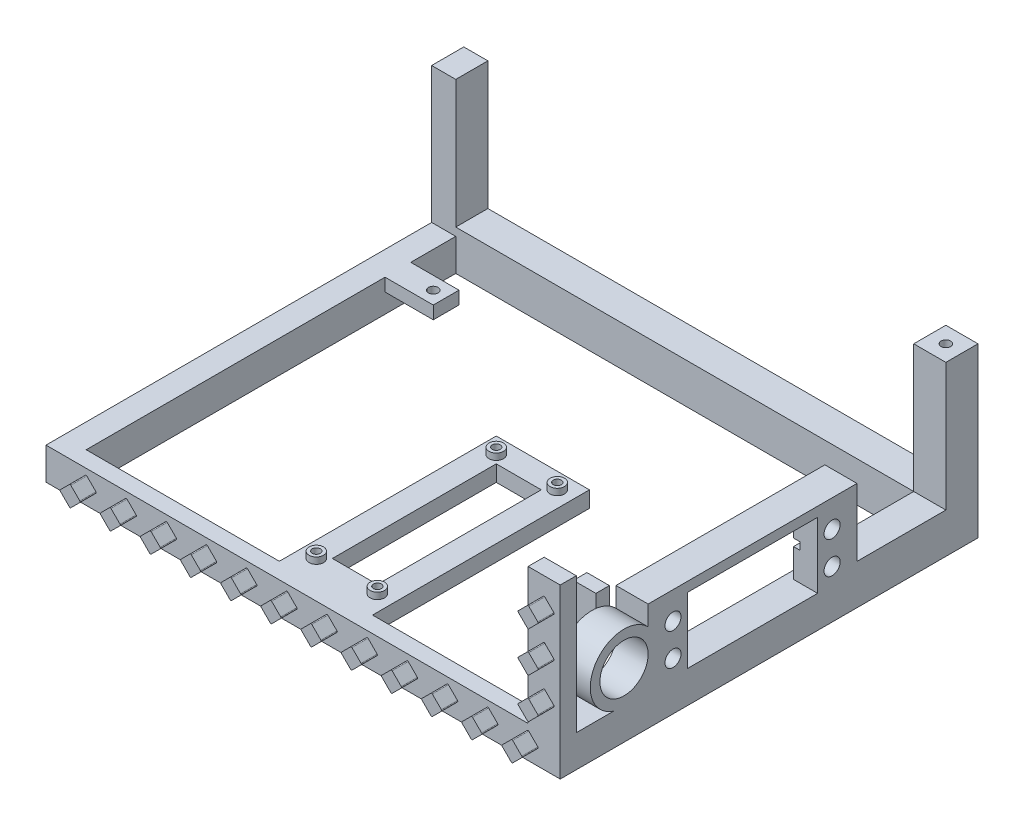
SolidWorks part; units mm, degrees
other "Markup1"
sketch "Sketch27" plane through (-85, 52.3, 65) normal (-0.8972, 0.4289, 0.105) x (0.3802, 0.6295, 0.6776)
ref_plane "Front Plane" through (0, 0, 0) normal (0, 0, 1) x (1, 0, 0)
ref_plane "Top Plane" through (0, 0, 0) normal (0, 1, 0) x (1, 0, 0)
ref_plane "Right Plane" through (0, 0, 0) normal (1, 0, 0) x (0, 0, -1)
sketch "Sketch1" plane through (0, 0, 0) normal (0, 1, 0) x (1, 0, 0)
  line L0 (0, 0) -> (0, 70) construction
  line L1 (-85, -60) -> (75, -60)
  line L2 (-85, -60) -> (-85, 70)
  line L3 (-85, 70) -> (75, 70)
  line L4 (75, -60) -> (75, 70)
  line L5 (0, 0) -> (0, -60) construction
  point P0 (0, 0)
  dimension "D1" = 160
  dimension "D2" = 70
  dimension "D3" = 60
extrude "Boss-Extrude1" add sketch "Sketch1" along normal blind 10
sketch "Sketch2" plane through (0, 10, 0) normal (0, 1, 0) x (1, 0, 0)
  line L0 (-85, 70) -> (75, 70)
  line L4 (-85, 70) -> (-85, 60)
  line L5 (-85, 70) -> (-85, -60) construction
  line L6 (-85, 60) -> (65, 60)
  line L13 (75, 70) -> (75, -60)
  line L14 (75, -60) -> (65, -60)
  line L15 (-85, -60) -> (75, -60) construction
  line L16 (65, -60) -> (65, 60)
extrude "Boss-Extrude2" add sketch "Sketch2" along normal blind 42.3
sketch "Sketch6" plane through (0, 0, 60) normal (0, 0, 1) x (1, 0, 0)
  line L0 (65, 10) -> (75, 10) construction
  line L1 (75, 52.3) -> (75, 0) construction
  line L2 (69.7879, 40.6121) -> (66.9621, 43.4379)
  line L79 (65, 10) -> (65, 0) construction
  line L156 (-85, 0) -> (75, 0) construction
  line L157 (66.9621, 43.8621) -> (69.7879, 46.6879)
  line L158 (70.2121, 46.6879) -> (73.0379, 43.8621)
  line L159 (70, 10) -> (70, 52.3) construction
  line L160 (65, 52.3) -> (75, 52.3) construction
  line L185 (65, 5) -> (-85, 5) construction
  line L186 (-85, 10) -> (-85, 0) construction
  line L187 (-10, 8.25) -> (-10, 1.75) construction
  line L188 (-10.2121, 8.0379) -> (-13.0379, 5.2121)
  line L189 (-13.0379, 4.7879) -> (-10.2121, 1.9621)
  line L190 (-9.7879, 1.9621) -> (-6.9621, 4.7879)
  line L191 (-6.9621, 5.2121) -> (-9.7879, 8.0379)
  line L192 (73.25, 31.15) -> (66.75, 31.15) construction
  line L193 (66.9621, 31.3621) -> (69.7879, 34.1879)
  line L194 (70.2121, 34.1879) -> (73.0379, 31.3621)
  line L195 (73.0379, 30.9379) -> (70.2121, 28.1121)
  line L196 (69.7879, 28.1121) -> (66.9621, 30.9379)
  line L197 (5.5379, 5.2121) -> (2.7121, 8.0379)
  line L198 (2.2879, 8.0379) -> (-0.5379, 5.2121)
  line L199 (-0.5379, 4.7879) -> (2.2879, 1.9621)
  line L200 (2.7121, 1.9621) -> (5.5379, 4.7879)
  line L201 (18.0379, 5.2121) -> (15.2121, 8.0379)
  line L202 (14.7879, 8.0379) -> (11.9621, 5.2121)
  line L203 (11.9621, 4.7879) -> (14.7879, 1.9621)
  line L204 (15.2121, 1.9621) -> (18.0379, 4.7879)
  line L205 (30.5379, 5.2121) -> (27.7121, 8.0379)
  line L206 (27.2879, 8.0379) -> (24.4621, 5.2121)
  line L207 (24.4621, 4.7879) -> (27.2879, 1.9621)
  line L208 (27.7121, 1.9621) -> (30.5379, 4.7879)
  line L209 (43.0379, 5.2121) -> (40.2121, 8.0379)
  line L210 (39.7879, 8.0379) -> (36.9621, 5.2121)
  line L211 (36.9621, 4.7879) -> (39.7879, 1.9621)
  line L212 (40.2121, 1.9621) -> (43.0379, 4.7879)
  line L213 (55.5379, 5.2121) -> (52.7121, 8.0379)
  line L214 (52.2879, 8.0379) -> (49.4621, 5.2121)
  line L215 (49.4621, 4.7879) -> (52.2879, 1.9621)
  line L216 (52.7121, 1.9621) -> (55.5379, 4.7879)
  line L217 (68.0379, 5.2121) -> (65.2121, 8.0379)
  line L218 (64.7879, 8.0379) -> (61.9621, 5.2121)
  line L219 (61.9621, 4.7879) -> (64.7879, 1.9621)
  line L220 (65.2121, 1.9621) -> (68.0379, 4.7879)
  line L221 (-19.4621, 5.2121) -> (-22.2879, 8.0379)
  line L222 (-22.7121, 8.0379) -> (-25.5379, 5.2121)
  line L223 (-25.5379, 4.7879) -> (-22.7121, 1.9621)
  line L224 (-22.2879, 1.9621) -> (-19.4621, 4.7879)
  line L225 (-31.9621, 5.2121) -> (-34.7879, 8.0379)
  line L226 (-35.2121, 8.0379) -> (-38.0379, 5.2121)
  line L227 (-38.0379, 4.7879) -> (-35.2121, 1.9621)
  line L228 (-34.7879, 1.9621) -> (-31.9621, 4.7879)
  line L229 (-44.4621, 5.2121) -> (-47.2879, 8.0379)
  line L230 (-47.7121, 8.0379) -> (-50.5379, 5.2121)
  line L231 (-50.5379, 4.7879) -> (-47.7121, 1.9621)
  line L232 (-47.2879, 1.9621) -> (-44.4621, 4.7879)
  line L233 (-56.9621, 5.2121) -> (-59.7879, 8.0379)
  line L234 (-60.2121, 8.0379) -> (-63.0379, 5.2121)
  line L235 (-63.0379, 4.7879) -> (-60.2121, 1.9621)
  line L236 (-59.7879, 1.9621) -> (-56.9621, 4.7879)
  line L237 (-69.4621, 5.2121) -> (-72.2879, 8.0379)
  line L238 (-72.7121, 8.0379) -> (-75.5379, 5.2121)
  line L239 (-75.5379, 4.7879) -> (-72.7121, 1.9621)
  line L240 (-72.2879, 1.9621) -> (-69.4621, 4.7879)
  line L241 (73.0379, 43.4379) -> (70.2121, 40.6121)
  line L242 (69.7879, 15.6121) -> (66.9621, 18.4379)
  line L243 (66.9621, 18.8621) -> (69.7879, 21.6879)
  line L244 (70.2121, 21.6879) -> (73.0379, 18.8621)
  line L245 (73.0379, 18.4379) -> (70.2121, 15.6121)
  arc A128 (-13.0379, 5.2121) -> (-13.0379, 4.7879) centre (-12.8257, 5) ccw
  arc A129 (-9.7879, 1.9621) -> (-10.2121, 1.9621) centre (-10, 2.1743) cw
  arc A130 (-6.9621, 4.7879) -> (-6.9621, 5.2121) centre (-7.1743, 5) ccw
  arc A131 (-9.7879, 8.0379) -> (-10.2121, 8.0379) centre (-10, 7.8257) ccw
  arc A132 (66.9621, 30.9379) -> (66.9621, 31.3621) centre (67.1743, 31.15) cw
  arc A133 (70.2121, 28.1121) -> (69.7879, 28.1121) centre (70, 28.3243) cw
  arc A134 (73.0379, 30.9379) -> (73.0379, 31.3621) centre (72.8257, 31.15) ccw
  arc A135 (69.7879, 34.1879) -> (70.2121, 34.1879) centre (70, 33.9757) cw
  arc A136 (2.7121, 8.0379) -> (2.2879, 8.0379) centre (2.5, 7.8257) ccw
  arc A137 (5.5379, 4.7879) -> (5.5379, 5.2121) centre (5.3257, 5) ccw
  arc A138 (-0.5379, 5.2121) -> (-0.5379, 4.7879) centre (-0.3257, 5) ccw
  arc A139 (2.7121, 1.9621) -> (2.2879, 1.9621) centre (2.5, 2.1743) cw
  arc A140 (15.2121, 8.0379) -> (14.7879, 8.0379) centre (15, 7.8257) ccw
  arc A141 (18.0379, 4.7879) -> (18.0379, 5.2121) centre (17.8257, 5) ccw
  arc A142 (11.9621, 5.2121) -> (11.9621, 4.7879) centre (12.1743, 5) ccw
  arc A143 (15.2121, 1.9621) -> (14.7879, 1.9621) centre (15, 2.1743) cw
  arc A144 (27.7121, 8.0379) -> (27.2879, 8.0379) centre (27.5, 7.8257) ccw
  arc A145 (30.5379, 4.7879) -> (30.5379, 5.2121) centre (30.3257, 5) ccw
  arc A146 (24.4621, 5.2121) -> (24.4621, 4.7879) centre (24.6743, 5) ccw
  arc A147 (27.7121, 1.9621) -> (27.2879, 1.9621) centre (27.5, 2.1743) cw
  arc A148 (40.2121, 8.0379) -> (39.7879, 8.0379) centre (40, 7.8257) ccw
  arc A149 (43.0379, 4.7879) -> (43.0379, 5.2121) centre (42.8257, 5) ccw
  arc A150 (36.9621, 5.2121) -> (36.9621, 4.7879) centre (37.1743, 5) ccw
  arc A151 (40.2121, 1.9621) -> (39.7879, 1.9621) centre (40, 2.1743) cw
  arc A152 (52.7121, 8.0379) -> (52.2879, 8.0379) centre (52.5, 7.8257) ccw
  arc A153 (55.5379, 4.7879) -> (55.5379, 5.2121) centre (55.3257, 5) ccw
  arc A154 (49.4621, 5.2121) -> (49.4621, 4.7879) centre (49.6743, 5) ccw
  arc A155 (52.7121, 1.9621) -> (52.2879, 1.9621) centre (52.5, 2.1743) cw
  arc A156 (65.2121, 8.0379) -> (64.7879, 8.0379) centre (65, 7.8257) ccw
  arc A157 (68.0379, 4.7879) -> (68.0379, 5.2121) centre (67.8257, 5) ccw
  arc A158 (61.9621, 5.2121) -> (61.9621, 4.7879) centre (62.1743, 5) ccw
  arc A159 (65.2121, 1.9621) -> (64.7879, 1.9621) centre (65, 2.1743) cw
  arc A160 (-22.2879, 8.0379) -> (-22.7121, 8.0379) centre (-22.5, 7.8257) ccw
  arc A161 (-19.4621, 4.7879) -> (-19.4621, 5.2121) centre (-19.6743, 5) ccw
  arc A162 (-25.5379, 5.2121) -> (-25.5379, 4.7879) centre (-25.3257, 5) ccw
  arc A163 (-22.2879, 1.9621) -> (-22.7121, 1.9621) centre (-22.5, 2.1743) cw
  arc A164 (-34.7879, 8.0379) -> (-35.2121, 8.0379) centre (-35, 7.8257) ccw
  arc A165 (-31.9621, 4.7879) -> (-31.9621, 5.2121) centre (-32.1743, 5) ccw
  arc A166 (-38.0379, 5.2121) -> (-38.0379, 4.7879) centre (-37.8257, 5) ccw
  arc A167 (-34.7879, 1.9621) -> (-35.2121, 1.9621) centre (-35, 2.1743) cw
  arc A168 (-47.2879, 8.0379) -> (-47.7121, 8.0379) centre (-47.5, 7.8257) ccw
  arc A169 (-44.4621, 4.7879) -> (-44.4621, 5.2121) centre (-44.6743, 5) ccw
  arc A170 (-50.5379, 5.2121) -> (-50.5379, 4.7879) centre (-50.3257, 5) ccw
  arc A171 (-47.2879, 1.9621) -> (-47.7121, 1.9621) centre (-47.5, 2.1743) cw
  arc A172 (-59.7879, 8.0379) -> (-60.2121, 8.0379) centre (-60, 7.8257) ccw
  arc A173 (-56.9621, 4.7879) -> (-56.9621, 5.2121) centre (-57.1743, 5) ccw
  arc A174 (-63.0379, 5.2121) -> (-63.0379, 4.7879) centre (-62.8257, 5) ccw
  arc A175 (-59.7879, 1.9621) -> (-60.2121, 1.9621) centre (-60, 2.1743) cw
  arc A176 (-72.2879, 8.0379) -> (-72.7121, 8.0379) centre (-72.5, 7.8257) ccw
  arc A177 (-69.4621, 4.7879) -> (-69.4621, 5.2121) centre (-69.6743, 5) ccw
  arc A178 (-75.5379, 5.2121) -> (-75.5379, 4.7879) centre (-75.3257, 5) ccw
  arc A179 (-72.2879, 1.9621) -> (-72.7121, 1.9621) centre (-72.5, 2.1743) cw
  arc A180 (70.2121, 40.6121) -> (69.7879, 40.6121) centre (70, 40.8243) cw
  arc A181 (66.9621, 43.4379) -> (66.9621, 43.8621) centre (67.1743, 43.65) cw
  arc A182 (69.7879, 46.6879) -> (70.2121, 46.6879) centre (70, 46.4757) cw
  arc A183 (73.0379, 43.4379) -> (73.0379, 43.8621) centre (72.8257, 43.65) ccw
  arc A184 (70.2121, 15.6121) -> (69.7879, 15.6121) centre (70, 15.8243) cw
  arc A185 (66.9621, 18.4379) -> (66.9621, 18.8621) centre (67.1743, 18.65) cw
  arc A186 (69.7879, 21.6879) -> (70.2121, 21.6879) centre (70, 21.4757) cw
  arc A187 (73.0379, 18.4379) -> (73.0379, 18.8621) centre (72.8257, 18.65) ccw
  point P19 (-10, 5)
  point P22 (-13.25, 5)
  point P28 (-6.75, 5)
  point P35 (70, 31.15)
  point P42 (70, 27.9)
  point P48 (70, 34.4)
  dimension "D2" = 0.3
  dimension "D1" = 0.3
  dimension "D3" = 2
  dimension "D4" = 2
extrude "Boss-Extrude3" add sketch "Sketch6" along normal blind 5
sketch "Sketch7" plane through (0, 10, 0) normal (0, 1, 0) x (1, 0, 0)
  line L0 (-66.5, 42) -> (-66.5, 60) construction
  line L1 (-85, 60) -> (65, 60) construction
  line L2 (-85, 60) -> (-85, -60) construction
  line L4 (-66.5, 42) -> (-85, 42) construction
  circle A0 centre (-66.5, 42) radius 1.5
  dimension "D1" = 18
  dimension "D2" = 18.5
extrude "Cut-Extrude2" cut sketch "Sketch7" against normal through all
sketch "Sketch8" plane through (0, 10, 0) normal (0, 1, 0) x (1, 0, 0)
  line L5 (-77.5, 60) -> (65, 60)
  line L6 (-66.5, 42) -> (-75, 42) construction
  line L7 (-77.5, 46) -> (-62.5, 46)
  line L8 (-62.5, 46) -> (-62.5, 38)
  line L9 (-62.5, 38) -> (-77.5, 38)
  line L11 (-77.5, 60) -> (-77.5, 46)
  line L12 (-85, 60) -> (-85, -60) construction
  line L13 (-77.5, 38) -> (-77.5, -55)
  line L14 (65, 60) -> (65, -55)
  line L15 (65, 60) -> (65, -60) construction
  line L16 (65, -55) -> (-77.5, -55)
  circle A0 centre (-66.5, 42) radius 1.5 construction
  dimension "D3" = 4
  dimension "D2" = 7.5
  dimension "D4" = 4
  dimension "D5" = 4
extrude "Cut-Extrude3" cut sketch "Sketch8" against normal through all contours L13 L16 L14 L5 L11 L7 L8 L9
sketch "Sketch11" plane through (0, 52.3, 0) normal (0, 1, 0) x (1, 0, 0)
  line L0 (75, 70) -> (65, 60) construction
  circle A3 centre (70, 65) radius 1.5
extrude "Cut-Extrude6" cut sketch "Sketch11" against normal blind 4
sketch "Sketch12" plane through (0, 0, -60) normal (0, 0, 1) x (1, 0, 0)
  line L1 (-77.5, 52.3) -> (-77.5, 12.5)
  line L7 (-77.5, 52.3) -> (65, 52.3)
  line L10 (-85, 52.3) -> (65, 52.3) construction
  line L12 (65, 52.3) -> (65, 12.5)
  line L13 (65, 52.3) -> (65, 0) construction
  line L14 (65, 12.5) -> (-77.5, 12.5)
extrude "Cut-Extrude7" cut sketch "Sketch12" against normal through all
sketch "Sketch15" plane through (0, 10, 0) normal (0, 1, 0) x (1, 0, 0)
  line L0 (6.6, 7.5) -> (6.6, -48.5) construction
  line L1 (6.6, 7.5) -> (-12.4, 7.5) construction
  line L2 (6.6, -48.5) -> (-12.4, -48.5) construction
  line L3 (-17.4, 12.5) -> (11.6, 12.5)
  line L4 (11.6, 12.5) -> (11.6, -53.5)
  line L6 (-12.4, -48.5) -> (-12.4, 7.5) construction
  line L9 (11.6, -53.5) -> (-17.4, -53.5)
  line L10 (-17.4, -53.5) -> (-17.4, 12.5)
  line L11 (-12.4, 7.5) -> (6.6, 7.5) construction
  line L23 (-77.5, 38) -> (-77.5, -55) construction
  line L24 (4.1, 5) -> (-9.9, 5)
  line L25 (4.1, 5) -> (4.1, -46)
  line L26 (4.1, -46) -> (-9.9, -46)
  line L27 (-9.9, 5) -> (-9.9, -46)
  line L33 (6.6, -48.5) -> (-12.4, -48.5) construction
  line L35 (6.6, -18.8362) -> (11.6, -18.8362) construction
  line L36 (-12.4, -20.5) -> (-17.4, -20.5) construction
  line L37 (-2.9, -48.5) -> (-2.9, -53.5) construction
  line L42 (-17.4, -53.5) -> (-17.4, -55)
  line L44 (-17.4, -55) -> (11.6, -55)
  line L45 (11.6, -55) -> (11.6, -53.5)
  circle A0 centre (-12.4, 7.5) radius 1.25
  circle A1 centre (6.6, 7.5) radius 1.25
  circle A2 centre (-12.4, -48.5) radius 1.25
  circle A3 centre (6.6, -48.5) radius 1.25
  circle A4 centre (-12.4, 7.5) radius 2.25
  circle A5 centre (6.6, 7.5) radius 2.25
  circle A6 centre (-12.4, -48.5) radius 2.25
  circle A7 centre (6.6, -48.5) radius 2.25
  point P32 (-2.9, -18.8362)
  dimension "D1" = 60.1
  dimension "D2" = 5
  dimension "D3" = 1.5
  dimension "D4" = 19
  dimension "D5" = 56
  dimension "D8" = 5
extrude "Boss-Extrude4" add sketch "Sketch15" against normal blind 5 contours L10 L9 A7 A6 A5 A4 L27 L24 L25 L26 | A7 A3 | A6 A2 | A5 A1 | A4 A0 | L45 L9 L42 region at (-2.9, 10, -11.7791) region at (-2.9, 10, 54.25) region at (-14.5864, 10, -7.5) region at (4.4136, 10, -7.5) region at (-14.5864, 10, 48.5) region at (4.4136, 10, 48.5)
extrude "Boss-Extrude5" add sketch "Sketch15<4>" along normal blind 2 contours A6 A2 | A7 A3 | A5 A1 | A4 A0 region at (-14.5864, 10, -7.5) region at (4.4136, 10, -7.5) region at (-14.5864, 10, 48.5) region at (4.4136, 10, 48.5)
sketch "Sketch15<4>" plane through (0, 10, 0) normal (0, 1, 0) x (1, 0, 0) same geometry as "Sketch15"
sketch "Sketch25" plane through (-85, 0, 0) normal (-1, 0, 0) x (0, 0, 1)
  line L0 (60, 5) -> (-60, 5) construction
  line L1 (60, 10) -> (60, 0) construction
  line L2 (-70, 52.3) -> (-70, 0) construction
  line L41 (-60, 10) -> (-70, 10) construction
  line L42 (-65, 10) -> (-65, 52.3) construction
  line L50 (-70, 52.3) -> (-60, 52.3) construction
  line L59 (-60, 10) -> (-60, 0) construction
  line L60 (-70, 0) -> (60, 0) construction
  line L61 (0, 8.425) -> (0, 1.575) construction
  line L62 (0, 8.425) -> (-3.425, 5)
  line L63 (-3.425, 5) -> (0, 1.575)
  line L64 (0, 1.575) -> (3.425, 5)
  line L65 (3.425, 5) -> (0, 8.425)
  line L66 (15.925, 5) -> (12.5, 8.425)
  line L67 (12.5, 8.425) -> (9.075, 5)
  line L68 (9.075, 5) -> (12.5, 1.575)
  line L69 (12.5, 1.575) -> (15.925, 5)
  line L70 (28.425, 5) -> (25, 8.425)
  line L71 (25, 8.425) -> (21.575, 5)
  line L72 (21.575, 5) -> (25, 1.575)
  line L73 (25, 1.575) -> (28.425, 5)
  line L74 (40.925, 5) -> (37.5, 8.425)
  line L75 (37.5, 8.425) -> (34.075, 5)
  line L76 (34.075, 5) -> (37.5, 1.575)
  line L77 (37.5, 1.575) -> (40.925, 5)
  line L78 (53.425, 5) -> (50, 8.425)
  line L79 (50, 8.425) -> (46.575, 5)
  line L80 (46.575, 5) -> (50, 1.575)
  line L81 (50, 1.575) -> (53.425, 5)
  line L82 (-9.075, 5) -> (-12.5, 8.425)
  line L83 (-12.5, 8.425) -> (-15.925, 5)
  line L84 (-15.925, 5) -> (-12.5, 1.575)
  line L85 (-12.5, 1.575) -> (-9.075, 5)
  line L86 (-21.575, 5) -> (-25, 8.425)
  line L87 (-25, 8.425) -> (-28.425, 5)
  line L88 (-28.425, 5) -> (-25, 1.575)
  line L89 (-25, 1.575) -> (-21.575, 5)
  line L90 (-34.075, 5) -> (-37.5, 8.425)
  line L91 (-37.5, 8.425) -> (-40.925, 5)
  line L92 (-40.925, 5) -> (-37.5, 1.575)
  line L93 (-37.5, 1.575) -> (-34.075, 5)
  line L94 (-46.575, 5) -> (-50, 8.425)
  line L95 (-50, 8.425) -> (-53.425, 5)
  line L96 (-53.425, 5) -> (-50, 1.575)
  line L97 (-50, 1.575) -> (-46.575, 5)
  line L98 (-59.075, 5) -> (-62.5, 8.425)
  line L99 (-62.5, 8.425) -> (-65.925, 5)
  line L100 (-65.925, 5) -> (-62.5, 1.575)
  line L101 (-62.5, 1.575) -> (-59.075, 5)
  line L114 (-61.575, 31.15) -> (-68.425, 31.15) construction
  line L115 (-68.425, 31.15) -> (-65, 34.575)
  line L116 (-65, 34.575) -> (-61.575, 31.15)
  line L117 (-61.575, 31.15) -> (-65, 27.725)
  line L118 (-65, 27.725) -> (-68.425, 31.15)
  line L119 (-65, 15.225) -> (-68.425, 18.65)
  line L120 (-68.425, 18.65) -> (-65, 22.075)
  line L121 (-65, 22.075) -> (-61.575, 18.65)
  line L122 (-61.575, 18.65) -> (-65, 15.225)
  line L123 (-65, 40.225) -> (-68.425, 43.65)
  line L124 (-68.425, 43.65) -> (-65, 47.075)
  line L125 (-65, 47.075) -> (-61.575, 43.65)
  line L126 (-61.575, 43.65) -> (-65, 40.225)
  point P10 (0, 5)
  point P54 (-65, 31.15)
  dimension "D1" = 5
  dimension "D3" = 2
  dimension "D2" = 6
  dimension "D4" = 2
extrude "Cut-Extrude20" cut sketch "Sketch25" against normal blind 5.25
sketch "Sketch26" plane through (0, 0, 0) normal (0, -1, 0) x (1, 0, 0)
  line L0 (-77.5, -46) -> (-77.5, -38)
  line L1 (-77.5, -38) -> (-62.5, -38)
  line L2 (-62.5, -38) -> (-62.5, -46)
  line L3 (-62.5, -46) -> (-77.5, -46)
extrude "Cut-Extrude21" cut sketch "Sketch26" against normal blind 6
sketch "Sketch36" plane through (65, 0, 0) normal (-1, 0, 0) x (0, 0, 1)
  line L0 (-27.35, 30.5) -> (-27.35, 10)
  line L1 (-27.35, 30.5) -> (27.65, 30.5)
  line L2 (-27.35, 10) -> (27.65, 10)
  line L3 (27.65, 10) -> (27.65, 30.5)
  line L7 (-70, 52.3) -> (60, 52.3) construction
  line L8 (-70, 12.5) -> (-70, 52.3) construction
  dimension "D1" = 21.8
  dimension "D3" = 42.65
  dimension "D4" = 20.5
extrude "Cut-Extrude27" cut sketch "Sketch36" against normal blind 2.5
sketch "Sketch37" plane through (67.5, 0, 0) normal (-1, 0, 0) x (0, 0, 1)
  line L0 (-20.1, 18.85) -> (-27.35, 18.85)
  line L1 (-27.35, 18.85) -> (-27.35, 21.15)
  line L2 (-27.35, 21.15) -> (-20.1, 21.15)
  line L4 (-20.1, 18.85) -> (-20.1, 21.15)
  line L6 (27.65, 30.5) -> (-27.35, 30.5) construction
  dimension "D1" = 9.35
extrude "Cut-Extrude28" cut sketch "Sketch37" against normal blind 2
sketch "Sketch38" plane through (67.5, 0, 0) normal (-1, 0, 0) x (0, 0, 1)
  line L4 (27.65, 30.5) -> (-27.35, 30.5) construction
  line L5 (-27.35, 30.5) -> (-27.35, 21.15) construction
  circle A0 centre (-24.6, 25) radius 2.5
  circle A1 centre (-24.6, 15) radius 2.5
  dimension "D4" = 5
  dimension "D1" = 5.5
  dimension "D2" = 10
  dimension "D3" = 2.75
sketch "Sketch39" plane through (65, 0, 0) normal (-1, 0, 0) x (0, 0, 1)
  line L0 (-60, 52.3) -> (-60, 12.5)
  line L1 (-60, 12.5) -> (-32.35, 12.5)
  line L2 (-32.35, 12.5) -> (-32.35, 33.5)
  line L3 (-32.35, 33.5) -> (55, 33.5)
  line L5 (-60, 52.3) -> (55, 52.3)
  line L6 (55, 52.3) -> (55, 33.5)
  line L7 (60, 52.3) -> (60, 10) construction
  dimension "D1" = 5
  dimension "D2" = 21
extrude "Cut-Extrude30" cut sketch "Sketch39" against normal blind 10
sketch "Sketch40" plane through (65, 0, 0) normal (-1, 0, 0) x (0, 0, 1)
  line L5 (55, 33.5) -> (32.65, 33.5)
  line L6 (-32.35, 33.5) -> (55, 33.5) construction
  line L7 (32.65, 33.5) -> (32.65, 10)
  line L8 (32.65, 10) -> (55, 10)
  line L9 (55, 33.5) -> (55, 10)
  circle A0 centre (40.15, 20) radius 7.5
  arc A1 (32.65, 12.6515) -> (36.9484, 10) centre (40.15, 20) ccw
  arc A2 (43.3516, 10) -> (32.65, 27.3485) centre (40.15, 20) ccw
  line M7 (55, 33.5) -> (-32.35, 33.5)
extrude "Cut-Extrude32" cut sketch "Sketch40" against normal blind 10 contours A2 L8 L9 L7 M7 | A0 region at (65, 21.75, 54.6757) region at (65, 20, 40.15)
sketch "Sketch41" plane through (67.5, 0, 0) normal (-1, 0, 0) x (0, 0, 1)
  line L0 (-20.1, 30.5) -> (20.4, 30.5)
  line L1 (20.4, 30.5) -> (20.4, 10)
  line L2 (20.4, 10) -> (-20.1, 10)
  line L3 (-20.1, 10) -> (-20.1, 30.5)
  line L5 (-32.35, 12.5) -> (-32.35, 33.5) construction
  line L6 (32.65, 33.5) -> (32.65, 27.3485) construction
  dimension "D1" = 12.25
  dimension "D2" = 12.25
extrude "Cut-Extrude33" cut sketch "Sketch38" against normal blind 10
extrude "Cut-Extrude34" cut sketch "Sketch41" against normal blind 10
ref_plane "Plane2" through (0, 0, 0.15) normal (0, 0, 1) x (1, 0, 0)
mirror "Mirror1" about plane through (0, 0, 0.15) normal (0, 0, 1) of "Cut-Extrude28", "Cut-Extrude33"
sketch "Sketch48" plane through (65, 0, 0) normal (-1, 0, 0) x (0, 0, 1)
  line L0 (24.4, 10) -> (20.2, 10)
  line L1 (20.2, 10) -> (20.2, 7)
  line L2 (20.2, 7) -> (24.4, 7)
  line L3 (24.4, 7) -> (24.4, 10)
  line L4 (-27.35, 10) -> (27.65, 10) construction
  dimension "D1" = 4.2
extrude "Boss-Extrude9" add sketch "Sketch48" along normal blind 21.5
sketch "Sketch49" plane through (0, 10, 0) normal (0, 1, 0) x (1, 0, 0)
  line L0 (43.5, -24.4) -> (43.5, -20.2)
  line L1 (43.5, -20.2) -> (50.5, -20.2)
  line L2 (43.5, -20.2) -> (65, -20.2) construction
  line L3 (50.5, -20.2) -> (50.5, -24.4)
  line L4 (43.5, -24.4) -> (65, -24.4) construction
  line L5 (50.5, -24.4) -> (43.5, -24.4)
extrude "Boss-Extrude10" add sketch "Sketch49" along normal blind 10
